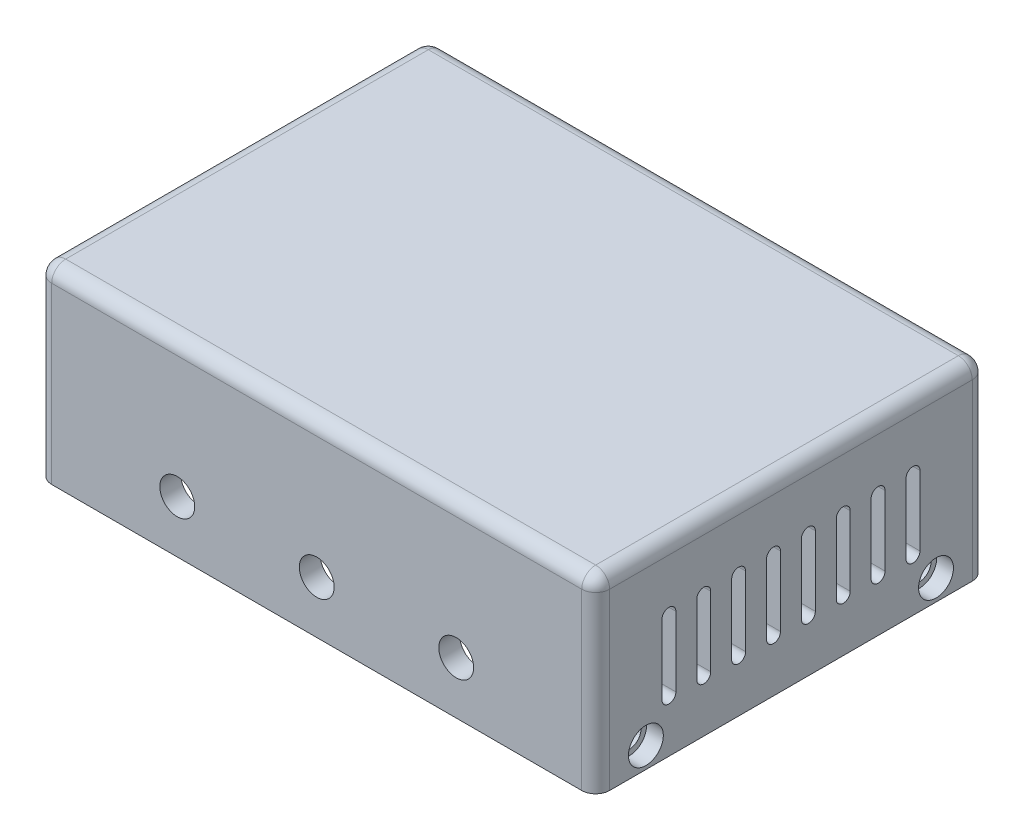
SolidWorks part; units mm, degrees
ref_plane "Front Plane" through (0, 0, 0) normal (0, 0, 1) x (1, 0, 0)
ref_plane "Top Plane" through (0, 0, 0) normal (0, 1, 0) x (1, 0, 0)
ref_plane "Right Plane" through (0, 0, 0) normal (1, 0, 0) x (0, 0, -1)
sketch "Sketch1" plane through (0, 0, 0) normal (0, 1, 0) x (1, 0, 0)
  line L1 (-40, 28) -> (40, 28)
  line L2 (-40, 28) -> (-40, -28)
  line L3 (-40, -28) -> (40, -28)
  line L4 (40, 28) -> (40, -28)
  line L5 (-40, 28) -> (40, -28) construction
  line L6 (-40, -28) -> (40, 28) construction
  point P0 (0, 0)
  dimension "D1" = 80
  dimension "D2" = 56
extrude "Boss-Extrude1" add sketch "Sketch1" along normal blind 3
sketch "Sketch2" plane through (0, 0, 0) normal (0, -1, 0) x (1, 0, 0)
  line L1 (37, -28) -> (-37, -28)
  line L3 (37, -28) -> (40, -28)
  line L4 (37, -25) -> (-37, -25)
  line L6 (37, 25) -> (37, -28)
  line L7 (-37, 25) -> (37, 25)
  line L8 (-37, -28) -> (-37, 25)
  line L9 (37, 25) -> (37, -25)
  line L10 (-37, 25) -> (37, 25)
  line L11 (-37, -25) -> (-37, 25)
  line L13 (40, -28) -> (40, 28)
  line L14 (40, 28) -> (-40, 28)
  line L15 (-40, 28) -> (-40, -28)
  line L16 (-40, -28) -> (40, -28)
  line L17 (40, -28) -> (40, 28)
  line L18 (40, 28) -> (-40, 28)
  line L19 (-40, 28) -> (-40, -28)
  line L20 (-40, -28) -> (-37, -28)
  dimension "D3" = 3
  dimension "D1" = 3
  dimension "D2" = 0
extrude "Boss-Extrude2" add sketch "Sketch2" along normal blind 24
fillet "Fillet1" radius 1 4 edges at (37, -12, 25) (37, -12, -25) (-37, -12, -25) (-37, -12, 25)
fillet "Fillet2" radius 2 8 edges at (-40, -10.5, -28) (-40, -10.5, 28) (0, 3, -28) (-40, 3, 0) (0, 3, 28) (40, 3, 0) (40, -10.5, 28) (40, -10.5, -28)
sketch "Sketch3" plane through (0, 0, 28) normal (0, 0, 1) x (1, 0, 0)
  line L0 (38, -24) -> (-38, -24) construction
  circle A0 centre (0, -16.5) radius 2.5
  circle A1 centre (-20, -16.5) radius 2.5
  circle A2 centre (20, -16.5) radius 2.5
  point P2 (0, 0)
  point P10 (0, 0)
  point P13 (0, 0)
  point P15 (0, 0)
  point P16 (0, 0)
  dimension "D1" = 5
  dimension "D2" = 5
  dimension "D4" = 7.5
  dimension "D3" = 20
extrude "Cut-Extrude1" cut sketch "Sketch3" against normal blind 10
sketch "Sketch5" plane through (0, 0, -28) normal (0, 0, -1) x (-1, 0, 0)
  line L0 (-27, -4) -> (-23, -4) construction
  line L1 (-27, -1) -> (-23, -1)
  line L2 (-27, -7) -> (-23, -7)
  line L3 (38, 1) -> (-38, 1) construction
  line L4 (-38, 1) -> (-38, -24) construction
  arc A0 (-27, -1) -> (-27, -7) centre (-27, -4) ccw
  arc A1 (-23, -7) -> (-23, -1) centre (-23, -4) ccw
  point P2 (-25, -4)
  dimension "D2" = 3
  dimension "D1" = 4
  dimension "D3" = 5
  dimension "D4" = 13
extrude "Cut-Extrude2" cut sketch "Sketch5" against normal blind 10
fillet "Fillet3" radius 2 4 edges at (25, -7, -28) (30, -4, -28) (20, -4, -28) (25, -1, -28)
sketch "Sketch6" plane through (0, 0, 0) normal (0, -1, 0) x (1, 0, 0)
  line L0 (37, -24) -> (37, 24) construction
  line L1 (37, 18.5) -> (33, 18.5)
  line L2 (37, 18.5) -> (37, 25)
  line L3 (37, 25) -> (30.5, 25)
  line L4 (30.5, 21) -> (30.5, 25)
  line L5 (36, 25) -> (-36, 25) construction
  line L18 (37, 10) -> (-29, 10) construction
  line L19 (37, -5) -> (30.5, -5)
  line L20 (30.5, -1) -> (30.5, -5)
  line L21 (37, 1.5) -> (33, 1.5)
  line L22 (37, 1.5) -> (37, -5)
  line L23 (4, -5) -> (4, 25) construction
  line L24 (-29, 1.5) -> (-25, 1.5)
  line L25 (-29, 1.5) -> (-29, -5)
  line L26 (-29, -5) -> (-22.5, -5)
  line L27 (-22.5, -1) -> (-22.5, -5)
  line L28 (-29, 25) -> (-22.5, 25)
  line L29 (-22.5, 21) -> (-22.5, 25)
  line L30 (-29, 18.5) -> (-25, 18.5)
  line L31 (-29, 18.5) -> (-29, 25)
  arc A2 (33, 18.5) -> (30.5, 21) centre (33, 21) cw
  arc A3 (33, 1.5) -> (30.5, -1) centre (33, -1) ccw
  arc A4 (-25, 1.5) -> (-22.5, -1) centre (-25, -1) cw
  arc A5 (-25, 18.5) -> (-22.5, 21) centre (-25, 21) ccw
  point P17 (4, 10)
  point P22 (-25, 20)
  point P25 (-25, -2)
  point P28 (30.5, 18.5)
  point P31 (32, -2)
  dimension "D1" = 6.5
  dimension "D2" = 6.5
  dimension "D3" = 66
  dimension "D4" = 30
extrude "Boss-Extrude3" add sketch "Sketch6" along normal blind 2
sketch "Sketch7" plane through (-40, 0, 0) normal (-1, 0, 0) x (0, 0, 1)
  line L0 (-17.5, -6.5) -> (-17.5, -16.5) construction
  line L1 (-16.5, -6.5) -> (-16.5, -16.5)
  line L2 (-18.5, -6.5) -> (-18.5, -16.5)
  line L3 (-26, 1) -> (-26, -24) construction
  line L4 (-12.5, -6.5) -> (-12.5, -16.5) construction
  line L5 (-11.5, -6.5) -> (-11.5, -16.5)
  line L6 (-13.5, -6.5) -> (-13.5, -16.5)
  line L7 (-7.5, -6.5) -> (-7.5, -16.5) construction
  line L8 (-6.5, -6.5) -> (-6.5, -16.5)
  line L9 (-8.5, -6.5) -> (-8.5, -16.5)
  line L10 (-2.5, -6.5) -> (-2.5, -16.5) construction
  line L11 (-1.5, -6.5) -> (-1.5, -16.5)
  line L12 (-3.5, -6.5) -> (-3.5, -16.5)
  line L13 (2.5, -6.5) -> (2.5, -16.5) construction
  line L14 (3.5, -6.5) -> (3.5, -16.5)
  line L15 (1.5, -6.5) -> (1.5, -16.5)
  line L16 (7.5, -6.5) -> (7.5, -16.5) construction
  line L17 (8.5, -6.5) -> (8.5, -16.5)
  line L18 (6.5, -6.5) -> (6.5, -16.5)
  line L19 (12.5, -6.5) -> (12.5, -16.5) construction
  line L20 (13.5, -6.5) -> (13.5, -16.5)
  line L21 (11.5, -6.5) -> (11.5, -16.5)
  line L22 (17.5, -6.5) -> (17.5, -16.5) construction
  line L23 (18.5, -6.5) -> (18.5, -16.5)
  line L24 (16.5, -6.5) -> (16.5, -16.5)
  arc A0 (-16.5, -6.5) -> (-18.5, -6.5) centre (-17.5, -6.5) ccw
  arc A1 (-18.5, -16.5) -> (-16.5, -16.5) centre (-17.5, -16.5) ccw
  arc A2 (-11.5, -6.5) -> (-13.5, -6.5) centre (-12.5, -6.5) ccw
  arc A3 (-13.5, -16.5) -> (-11.5, -16.5) centre (-12.5, -16.5) ccw
  arc A4 (-6.5, -6.5) -> (-8.5, -6.5) centre (-7.5, -6.5) ccw
  arc A5 (-8.5, -16.5) -> (-6.5, -16.5) centre (-7.5, -16.5) ccw
  arc A6 (-1.5, -6.5) -> (-3.5, -6.5) centre (-2.5, -6.5) ccw
  arc A7 (-3.5, -16.5) -> (-1.5, -16.5) centre (-2.5, -16.5) ccw
  arc A8 (3.5, -6.5) -> (1.5, -6.5) centre (2.5, -6.5) ccw
  arc A9 (1.5, -16.5) -> (3.5, -16.5) centre (2.5, -16.5) ccw
  arc A10 (8.5, -6.5) -> (6.5, -6.5) centre (7.5, -6.5) ccw
  arc A11 (6.5, -16.5) -> (8.5, -16.5) centre (7.5, -16.5) ccw
  arc A12 (13.5, -6.5) -> (11.5, -6.5) centre (12.5, -6.5) ccw
  arc A13 (11.5, -16.5) -> (13.5, -16.5) centre (12.5, -16.5) ccw
  arc A14 (18.5, -6.5) -> (16.5, -6.5) centre (17.5, -6.5) ccw
  arc A15 (16.5, -16.5) -> (18.5, -16.5) centre (17.5, -16.5) ccw
  point P2 (-17.5, -11.5)
  point P9 (-26, -11.5)
  point P13 (-12.5, -11.5)
  point P20 (-7.5, -11.5)
  point P27 (-2.5, -11.5)
  point P34 (2.5, -11.5)
  point P41 (7.5, -11.5)
  point P48 (12.5, -11.5)
  point P55 (17.5, -11.5)
  dimension "D1" = 1
  dimension "D2" = 10
  dimension "D3" = 8.5
  dimension "D4" = 8
extrude "Cut-Extrude3" cut sketch "Sketch7" against normal through all
hole_wizard "CBORE for M3 Cross Recess Pan Head Screw1" positions "3DSketch1" profile "Sketch9" counterbore size "M3" standard "IS" end condition up to next
sketch3d "3DSketch1"
  line L0 (40, -24, -26) -> (40, 1, -26) construction
  line L1 (40, -24, -26) -> (40, -24, 26) construction
  point P0 (40, -21, -20.8)
  point P6 (0, -22.6323, -35.9195)
  point P8 (0, -22.2303, -35.6495)
  point P10 (0, -22.2303, -35.6495)
  dimension "D1" = 5.2
  dimension "D2" = 3
sketch "Sketch9" plane through (40, -21, -20.8) normal (0, 1, 0) x (0, 0, -1)
  line L0 (0, 0) -> (0, 3)
  line L1 (0, 3) -> (1.7, 3)
  line L3 (1.7, 3) -> (1.7, 2.4)
  line L4 (1.7, 2.4) -> (2.5, 2.4)
  line L5 (2.5, 2.4) -> (2.5, 0)
  line L7 (2.5, 0) -> (0, 0)
  line L11 (0, -6.35) -> (0, 107.95) construction
  dimension "Thru Hole Dia." = 3.4
  dimension "Thru Hole Depth" = 3
  dimension "C'Bore Dia." = 5
  dimension "C'Bore Depth" = 2.4
mirror "Mirror1" about plane through (0, 0, 0) normal (0, 0, 1) of "CBORE for M3 Cross Recess Pan Head Screw1"
mirror "Mirror2" about plane through (0, 0, 0) normal (1, 0, 0) of "Mirror1"
